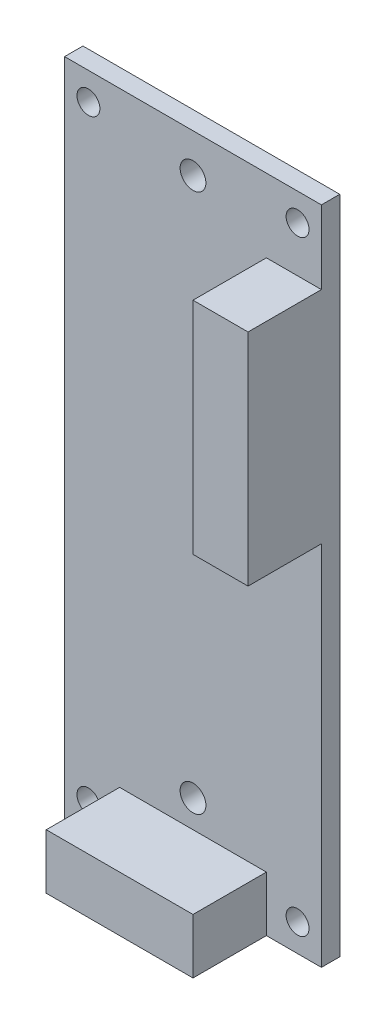
SolidWorks part; units mm, degrees
material "Printed Circuit Board"
ref_plane "Front Plane" through (0, 0, 0) normal (0, 0, 1) x (1, 0, 0)
ref_plane "Top Plane" through (0, 0, 0) normal (0, 1, 0) x (1, 0, 0)
ref_plane "Right Plane" through (0, 0, 0) normal (1, 0, 0) x (0, 0, -1)
sketch "Sketch1" plane through (0, 0, 0) normal (0, 0, 1) x (1, 0, 0)
  line L1 (-17.78, -45.72) -> (17.78, -45.72)
  line L2 (-17.78, -45.72) -> (-17.78, 45.72)
  line L3 (-17.78, 45.72) -> (17.78, 45.72)
  line L4 (17.78, -45.72) -> (17.78, 45.72)
  line L5 (-17.78, -45.72) -> (17.78, 45.72) construction
  line L6 (-17.78, 45.72) -> (17.78, -45.72) construction
  point P0 (0, 0)
  dimension "D1" = 91.44
  dimension "D2" = 35.56
extrude "Extrude1" add sketch "Sketch1" along normal blind 2.54
sketch "Sketch2" plane through (0, 0, 2.54) normal (0, 0, 1) x (1, 0, 0)
  line L0 (0, 45.72) -> (0, 41.91) construction
  line L1 (17.78, 45.72) -> (-17.78, 45.72) construction
  line L2 (0, 41.91) -> (14.478, 41.91) construction
  dimension "D1" = 3.81
  dimension "D2" = 14.478
hole_wizard "1/8 (0.125) Diameter Hole1" positions "3DSketch1" profile "Sketch3" hole size "1/8" standard "Ansi Inch"
sketch3d "3DSketch1"
  point P0 (14.478, 41.91, 2.54)
sketch "Sketch3" plane through (14.478, 41.91, 2.54) normal (1, 0, 0) x (0, -1, 0)
  line L0 (0, 0) -> (0, 16.1939)
  line L1 (0, 16.1939) -> (1.5875, 15.24)
  line L2 (1.5875, 15.24) -> (1.5875, 0)
  line L5 (1.5875, 0) -> (0, 0)
  line L10 (0, 16.1939) -> (-1.5875, 15.24) construction
  line L11 (0, -6.35) -> (0, 107.95) construction
  dimension "Hole Dia." = 3.175
  dimension "Hole Depth" = 15.24
  dimension "Drill Angle" = 118
mirror "Mirror1" about plane through (0, 0, 0) normal (1, 0, 0) of "1/8 (0.125) Diameter Hole1"
mirror "Mirror2" about plane through (0, 0, 0) normal (0, 1, 0) of "Mirror1"
sketch "Sketch4" plane through (0, 0, 2.54) normal (0, 0, 1) x (1, 0, 0)
  line L0 (0, -45.72) -> (0, -34.29) construction
  line L1 (-17.78, -45.72) -> (17.78, -45.72) construction
  line L2 (0, -34.29) -> (0, 41.148) construction
  dimension "D1" = 11.43
  dimension "D2" = 75.438
hole_wizard "#28 (0.1405) Diameter Hole1" positions "3DSketch2" profile "Sketch5" hole size "#28" standard "Ansi Inch"
sketch3d "3DSketch2"
  line L0 (0, -34.29, 2.54) -> (0, 41.148, 2.54) construction
  point P0 (0, -34.29, 2.54)
  point P3 (0, 40.3499, 2.54)
sketch "Sketch5" plane through (0, -34.29, 2.54) normal (1, 0, 0) x (0, -1, 0)
  line L0 (0, 0) -> (0, 16.3121)
  line L1 (0, 16.3121) -> (1.7843, 15.24)
  line L2 (1.7843, 15.24) -> (1.7843, 0)
  line L5 (1.7843, 0) -> (0, 0)
  line L10 (0, 16.3121) -> (-1.7844, 15.24) construction
  line L11 (0, -6.35) -> (0, 107.95) construction
  dimension "Hole Dia." = 3.5687
  dimension "Hole Depth" = 15.24
  dimension "Drill Angle" = 118
sketch "Sketch6" plane through (0, 0, 2.54) normal (0, 0, 1) x (1, 0, 0)
  line L0 (0, -45.72) -> (10.16, -45.72)
  line L1 (-17.78, -45.72) -> (17.78, -45.72) construction
  line L2 (10.16, -45.72) -> (10.16, -38.1)
  line L3 (10.16, -38.1) -> (-10.16, -38.1)
  line L4 (-10.16, -38.1) -> (-10.16, -45.72)
  line L5 (-10.16, -45.72) -> (0, -45.72)
  dimension "D1" = 20.32
  dimension "D2" = 7.62
extrude "Extrude2" add sketch "Sketch6" along normal blind 10.16
sketch "Sketch7" plane through (0, 0, 2.54) normal (0, 0, 1) x (1, 0, 0)
  line L0 (17.78, 45.72) -> (17.78, 35.56) construction
  line L1 (17.78, -45.72) -> (17.78, 45.72) construction
  line L2 (17.78, 35.56) -> (10.16, 35.56)
  line L3 (10.16, 35.56) -> (10.16, 5.08)
  line L4 (10.16, 5.08) -> (17.78, 5.08)
  line L5 (17.78, 5.08) -> (17.78, 35.56)
  dimension "D1" = 30.48
  dimension "D2" = 10.16
  dimension "D3" = 7.62
extrude "Extrude3" add sketch "Sketch7" along normal blind 10.16
